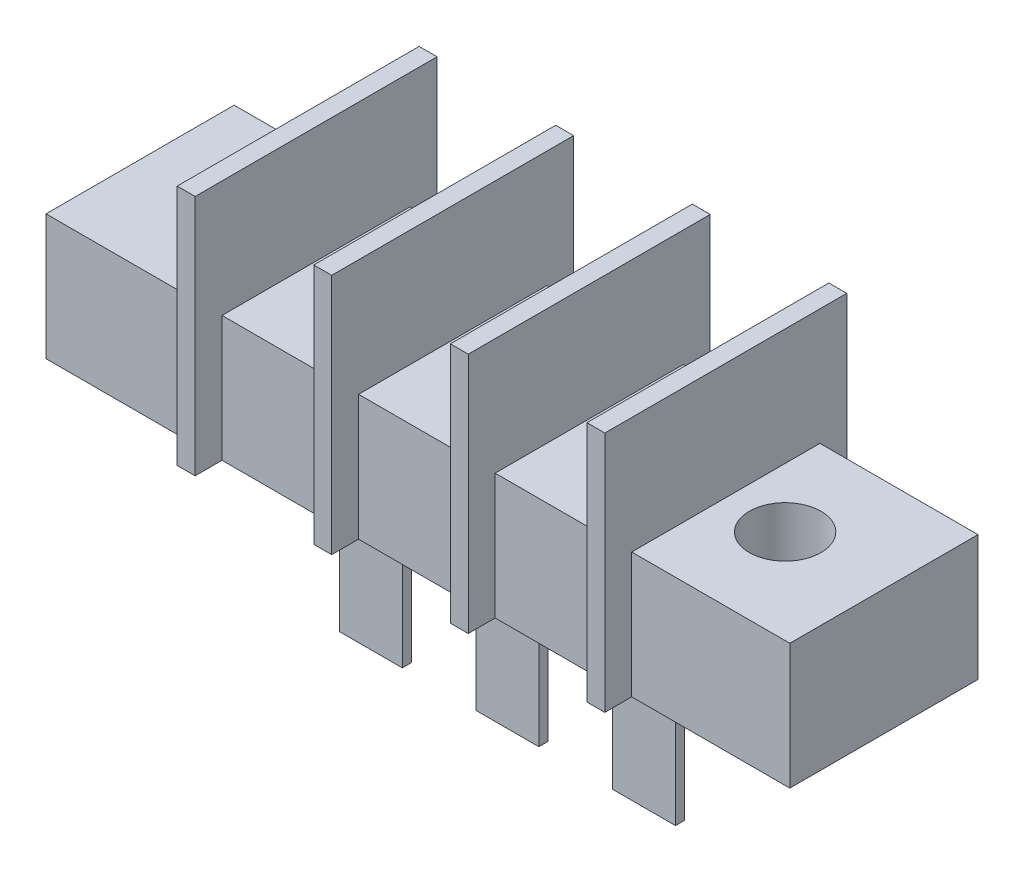
SolidWorks part; units mm, degrees
ref_plane "前视基准面" through (0, 0, 0) normal (0, 0, 1) x (1, 0, 0)
ref_plane "上视基准面" through (0, 0, 0) normal (0, 1, 0) x (1, 0, 0)
ref_plane "右视基准面" through (0, 0, 0) normal (1, 0, 0) x (0, 0, -1)
sketch "草图1" plane through (0, 0, 0) normal (0, 1, 0) x (1, 0, 0)
  line L0 (0, 12.7565) -> (0, -11.1323) construction
  line L1 (-20.75, -6.75) -> (20.75, -6.75)
  line L2 (-20.75, -6.75) -> (-20.75, 6.75)
  line L3 (-20.75, 6.75) -> (20.75, 6.75)
  line L4 (20.75, -6.75) -> (20.75, 6.75)
  line L5 (-29.1602, 0) -> (32.7116, 0) construction
  dimension "D1" = 41.5
  dimension "D2" = 13.5
extrude "拉伸1" add sketch "草图1" along normal blind 13.5
sketch "草图6" plane through (0, 0, 0) normal (0, -1, 0) x (1, 0, 0)
  line L0 (0, 12.0415) -> (0, -12.1791) construction
  line L1 (-6.3388, 0) -> (5.5048, 0) construction
  line L2 (1.75, 0.25) -> (-1.75, 0.25)
  line L3 (1.75, 0.25) -> (1.75, -0.25)
  line L4 (1.75, -0.25) -> (-1.75, -0.25)
  line L5 (-1.75, 0.25) -> (-1.75, -0.25)
  line L6 (9.37, 0.25) -> (5.87, 0.25)
  line L7 (9.37, 0.25) -> (9.37, -0.25)
  line L8 (9.37, -0.25) -> (5.87, -0.25)
  line L9 (5.87, 0.25) -> (5.87, -0.25)
  line L10 (1.75, 0.25) -> (9.37, 0.25) construction
  line L11 (-5.87, 0.25) -> (-5.87, -0.25)
  line L12 (-9.37, -0.25) -> (-5.87, -0.25)
  line L13 (-9.37, 0.25) -> (-9.37, -0.25)
  line L14 (-9.37, 0.25) -> (-5.87, 0.25)
  dimension "D1" = 0.5
  dimension "D2" = 3.5
  dimension "D3" = 7.62
extrude "拉伸2" add sketch "草图6" along normal blind 10
sketch "草图7" plane through (0, 13.5, 0) normal (0, 1, 0) x (1, 0, 0)
  line L0 (-24.5233, 0) -> (24.155, 0) construction
  line L1 (0, 10.4409) -> (0, -10.8197) construction
  line L2 (20.75, 6.75) -> (-20.75, 6.75) construction
  line L3 (-4.31, 6.75) -> (-3.31, 6.75)
  line L4 (-4.31, 6.75) -> (-4.31, -6.75)
  line L5 (-4.31, -6.75) -> (-3.31, -6.75)
  line L6 (-3.31, 6.75) -> (-3.31, -6.75)
  line L7 (-20.75, -6.75) -> (20.75, -6.75) construction
  line L8 (-3.81, 12.9669) -> (-3.81, -10.3987) construction
  line L9 (3.31, 6.75) -> (4.31, 6.75)
  line L10 (3.31, 6.75) -> (3.31, -6.75)
  line L11 (3.31, -6.75) -> (4.31, -6.75)
  line L12 (4.31, 6.75) -> (4.31, -6.75)
  line L13 (10.93, 6.75) -> (11.93, 6.75)
  line L14 (10.93, 6.75) -> (10.93, -6.75)
  line L15 (10.93, -6.75) -> (11.93, -6.75)
  line L16 (11.93, 6.75) -> (11.93, -6.75)
  line L17 (-11.93, 6.75) -> (-10.93, 6.75)
  line L18 (-11.93, 6.75) -> (-11.93, -6.75)
  line L19 (-11.93, -6.75) -> (-10.93, -6.75)
  line L20 (-10.93, 6.75) -> (-10.93, -6.75)
  dimension "D1" = 1
  dimension "D2" = 3.81
  dimension "D3" = 3
  dimension "D4" = 2
extrude "切除-拉伸1" cut sketch "草图7" against normal blind 6.5 flip side to cut
sketch "草图8" plane through (0, 0, 6.75) normal (0, 0, 1) x (1, 0, 0)
  line L0 (-20.75, 7) -> (-11.93, 7) construction
  line L1 (-20.75, 0) -> (-11.93, 0)
  line L2 (-20.75, 0) -> (-20.75, 7)
  line L3 (-20.75, 7) -> (-11.93, 7)
  line L4 (-11.93, 0) -> (-11.93, 7)
  line L5 (-11.93, 7) -> (-11.93, 13.5) construction
  line L6 (-20.75, 0) -> (20.75, 0) construction
  line L7 (-10.93, 7) -> (-4.31, 7)
  line L8 (-10.93, 7) -> (-10.93, 0)
  line L9 (-10.93, 0) -> (-4.31, 0)
  line L10 (-4.31, 7) -> (-4.31, 0)
  line L11 (-4.31, 7) -> (-4.31, 13.5) construction
  line L12 (1.75, 0) -> (-1.75, 0) construction
  line L13 (-3.31, 7) -> (3.31, 7)
  line L14 (-3.31, 7) -> (-3.31, 0)
  line L15 (-3.31, 0) -> (3.31, 0)
  line L16 (3.31, 7) -> (3.31, 0)
  line L17 (3.31, 7) -> (3.31, 13.5) construction
  line L18 (4.31, 7) -> (4.31, 13.5) construction
  line L19 (10.93, 7) -> (4.31, 7)
  line L20 (10.93, 7) -> (10.93, 0)
  line L21 (10.93, 0) -> (4.31, 0)
  line L22 (4.31, 7) -> (4.31, 0)
  line L23 (20.75, 7) -> (20.75, 0) construction
  line L24 (11.93, 7) -> (20.75, 7)
  line L25 (11.93, 7) -> (11.93, 0)
  line L26 (11.93, 0) -> (20.75, 0)
  line L27 (20.75, 7) -> (20.75, 0)
extrude "切除-拉伸2" cut sketch "草图8" against normal blind 1.5
mirror "镜向1" about plane through (0, 0, 0) normal (0, 0, 1) of "切除-拉伸2"
sketch "草图9" plane through (0, 7, 0) normal (0, 1, 0) x (1, 0, 0)
  line L0 (-26.0924, 0) -> (23.9297, 0) construction
  line L1 (0, 7.8873) -> (0, -16.7753) construction
  circle A0 centre (-15.24, 0) radius 2
  circle A1 centre (15.24, 0) radius 2
  dimension "D1" = 4
  dimension "D2" = 15.24
extrude "切除-拉伸3" cut sketch "草图9" against normal through all
